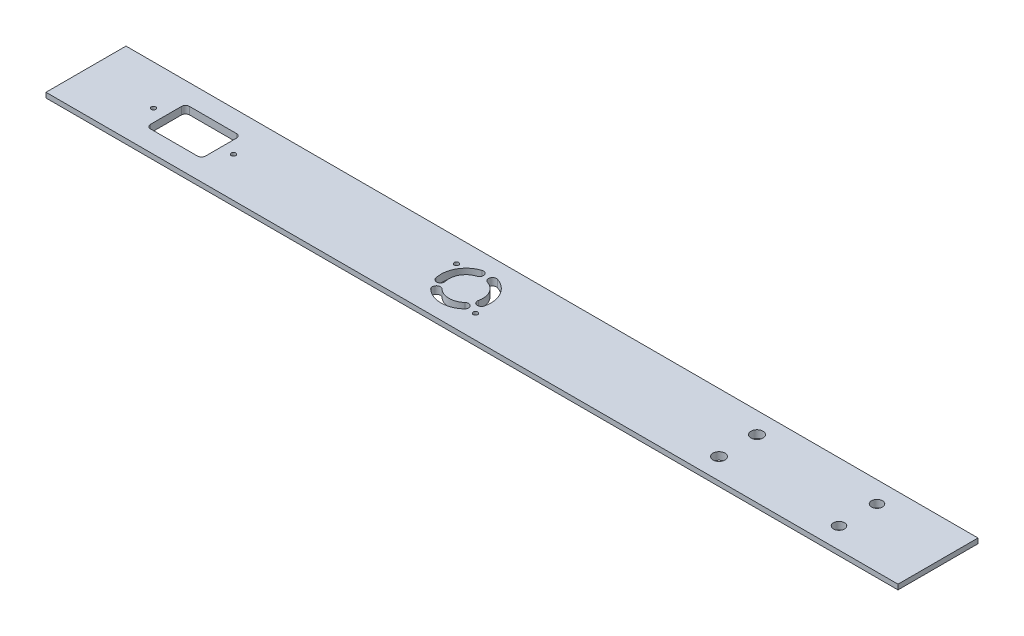
SolidWorks part; units mm, degrees
ref_plane "Спереди" through (0, 0, 0) normal (0, 0, 1) x (1, 0, 0)
ref_plane "Сверху" through (0, 0, 0) normal (0, 1, 0) x (1, 0, 0)
ref_plane "Справа" through (0, 0, 0) normal (1, 0, 0) x (0, 0, -1)
sketch "Эскиз1" plane through (0, 0, 0) normal (0, 1, 0) x (1, 0, 0)
  line L1 (-213, 20) -> (213, 20)
  line L2 (-213, 20) -> (-213, -20)
  line L3 (-213, -20) -> (213, -20)
  line L4 (213, 20) -> (213, -20)
  line L5 (-213, 20) -> (213, -20) construction
  line L6 (-213, -20) -> (213, 20) construction
  point P0 (0, 0)
  dimension "D1" = 40
  dimension "D2" = 426
extrude "Бобышка-Вытянуть1" add sketch "Эскиз1" along normal blind 3.7
extrude "Вырез-Вытянуть-Тонкостенный1" cut sketch "Эскиз1<2>" along normal blind 1.2 thin thin type one direction reverse wall 1.6
sketch "Эскиз1<2>" plane through (0, 0, 0) normal (0, 1, 0) x (1, 0, 0) same geometry as "Эскиз1"
sketch "Эскиз2" plane through (0, 0, 0) normal (0, 1, 0) x (1, 0, 0)
  line L0 (173, -9.5) -> (173, 9.5) construction
  line L1 (213, 20) -> (213, -20) construction
  line L2 (-213, 20) -> (-213, -20) construction
  line L3 (-173, 0) -> (-179.25, 0) construction
  line L4 (-173, -9.75) -> (-145.5, -9.75)
  line L5 (-173, -9.75) -> (-173, 9.75)
  line L6 (-173, 9.75) -> (-145.5, 9.75)
  line L7 (-145.5, -9.75) -> (-145.5, 9.75)
  line L8 (-145.5, 0) -> (-139.25, 0) construction
  line L9 (-23, 0) -> (-19.7553, 9.9861) construction
  line L10 (-12.804, -2.5085) -> (-23, 0) construction
  line L12 (-23, 0) -> (-23, 6.3318) construction
  circle A0 centre (173, -9.5) radius 2.75
  circle A2 centre (173, 9.5) radius 2.75
  circle A6 centre (-179.25, 0) radius 1.15
  circle A7 centre (-139.25, 0) radius 1.15
  circle A8 centre (113, 9.5) radius 3.0064
  circle A9 centre (113, -9.5) radius 3.0064
  arc A12 (-12.804, -2.5085) -> (-19.7553, 9.9861) centre (-23, 0) ccw construction
  arc A13 (-10.862, -2.9863) -> (-19.1373, 11.8882) centre (-23, 0) ccw
  arc A14 (-14.7461, -2.0307) -> (-20.3734, 8.084) centre (-23, 0) ccw
  arc A15 (-14.7461, -2.0307) -> (-10.862, -2.9863) centre (-12.804, -2.5085) ccw
  arc A16 (-19.1373, 11.8882) -> (-20.3734, 8.084) centre (-19.7553, 9.9861) ccw
  arc A17 (-26.2447, 9.9861) -> (-33.196, -2.5085) centre (-23, 0) ccw construction
  arc A18 (-26.8627, 11.8882) -> (-35.138, -2.9863) centre (-23, 0) ccw
  arc A19 (-25.6266, 8.084) -> (-31.2539, -2.0307) centre (-23, 0) ccw
  arc A20 (-25.6266, 8.084) -> (-26.8627, 11.8882) centre (-26.2447, 9.9861) ccw
  arc A21 (-35.138, -2.9863) -> (-31.2539, -2.0307) centre (-33.196, -2.5085) ccw
  arc A22 (-15.9347, -7.7673) -> (-30.2319, -7.6124) centre (-23, 0) cw construction
  arc A23 (-31.6094, -9.0624) -> (-14.5889, -9.2468) centre (-23, 0) ccw
  arc A24 (-28.8544, -6.1625) -> (-17.2805, -6.2878) centre (-23, 0) ccw
  arc A25 (-28.8544, -6.1625) -> (-31.6094, -9.0624) centre (-30.2319, -7.6124) ccw
  arc A26 (-14.5889, -9.2468) -> (-17.2805, -6.2878) centre (-15.9347, -7.7673) ccw
  circle A27 centre (-9.9, -8.35) radius 1.15
  circle A28 centre (-36.1, 8.35) radius 1.15
  point P5 (173, 0)
  point P9 (213, 0)
  point P11 (-13.8244, 5.1048)
  point P25 (-32.1756, 5.1048)
  point P41 (-23.1137, -10.4994)
  dimension "D2" = 5.5
  dimension "D5" = 12.5
  dimension "D14" = 2.3
  dimension "D6" = 2
  dimension "D9" = 2.3
  dimension "D3" = 19
  dimension "D4" = 40
  dimension "D7" = 190
  dimension "D8" = 18
  dimension "D10" = 19.5
  dimension "D11" = 27.5
  dimension "D12" = 40
  dimension "D13" = 40
  dimension "D15" = 60
extrude "Вырез-Вытянуть1" cut sketch "Эскиз2" along normal blind 6
fillet "Скругление1" radius 2 4 edges at (-145.5, 1.85, 9.75) (-173, 1.85, 9.75) (-145.5, 1.85, -9.75) (-173, 1.85, -9.75)
